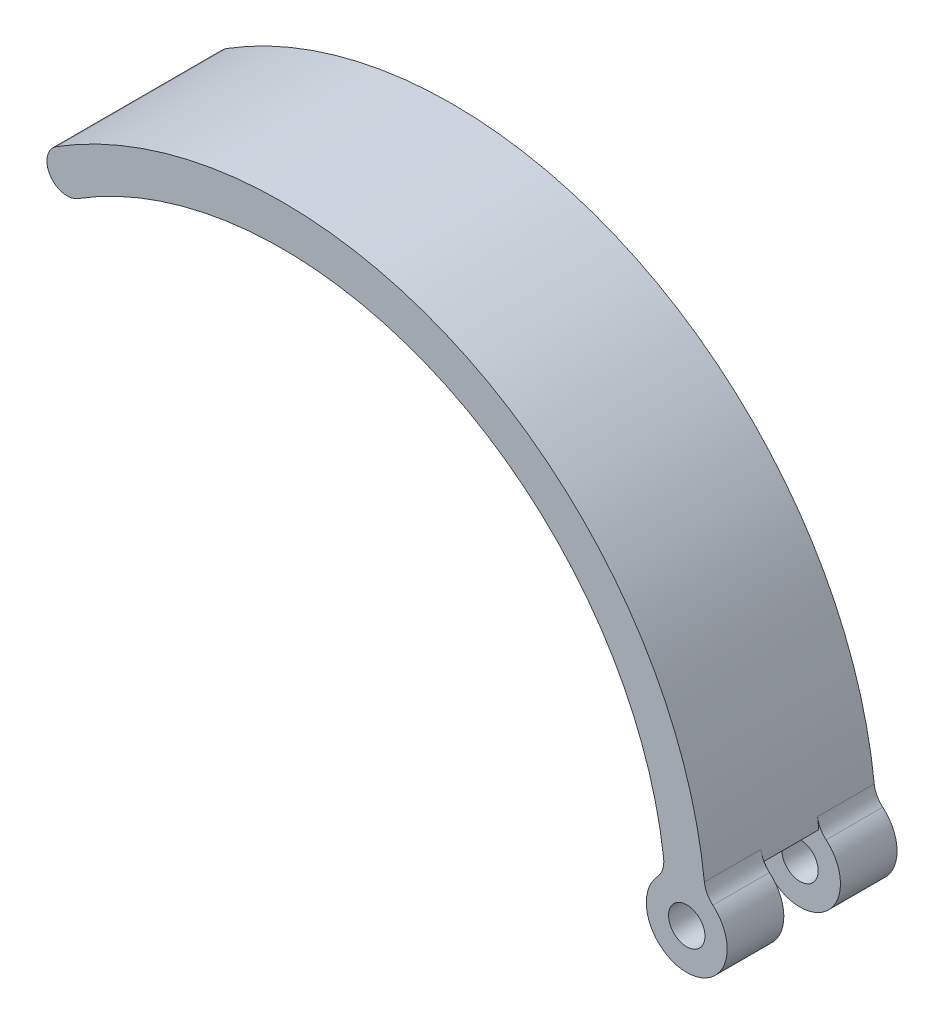
SolidWorks part; units mm, degrees
ref_plane "Plan de face" through (0, 0, 0) normal (0, 0, 1) x (1, 0, 0)
ref_plane "Plan de dessus" through (0, 0, 0) normal (0, 1, 0) x (1, 0, 0)
ref_plane "Plan de droite" through (0, 0, 0) normal (1, 0, 0) x (0, 0, -1)
sketch "Esquisse1" plane through (0, 0, 0) normal (0, 0, 1) x (1, 0, 0)
  line L0 (0, 0) -> (-28.6788, 40.9576) construction
  line L1 (0, 0) -> (50, 0) construction
  arc A0 (50, 0) -> (-28.6788, 40.9576) centre (0, 0) ccw
  dimension "D1" = 50
  dimension "D2" = 125
extrude "Extru.-Mince1" add sketch "Esquisse1" along normal blind 21 thin thin type mid plane wall 5
sketch "Esquisse4" plane through (0, 0, 21) normal (0, 0, 1) x (1, 0, 0)
  line L0 (52.5, 0) -> (47.5, 0) construction
  circle A0 centre (50, 0) radius 5
  dimension "D1" = 10
extrude "Boss.-Extru.2" add sketch "Esquisse4" against normal up to vertex (21 mm away) up to point (-30.1128, 43.0055, 0)
sketch "Esquisse5" plane through (0, 0, 21) normal (0, 0, 1) x (1, 0, 0)
  circle A0 centre (50, 0) radius 2.25
  dimension "D1" = 4.5
extrude "Enlèv. mat.-Extru.2" cut sketch "Esquisse5" against normal through all both and the other way through all
sketch "Esquisse6" plane through (0, 0, 21) normal (0, 0, 1) x (1, 0, 0)
  circle A0 centre (50, 0) radius 5
  arc A1 (47.3125, 4.2163) -> (52.3125, 4.4331) centre (50, 0) ccw construction
extrude "Enlèv. mat.-Extru.3" cut sketch "Esquisse6" against normal blind 7 from offset 7 offset against normal yes
fillet "Congé4" radius 3 4 edges at (52.3125, 4.4331, 3.5) (52.3125, 4.4331, 17.5) (47.3125, 4.2163, 17.5) (47.3125, 4.2163, 3.5)
fillet "Congé6" radius 2.5 2 edges at (-30.1128, 43.0055, 10.5) (-27.2449, 38.9097, 10.5)
